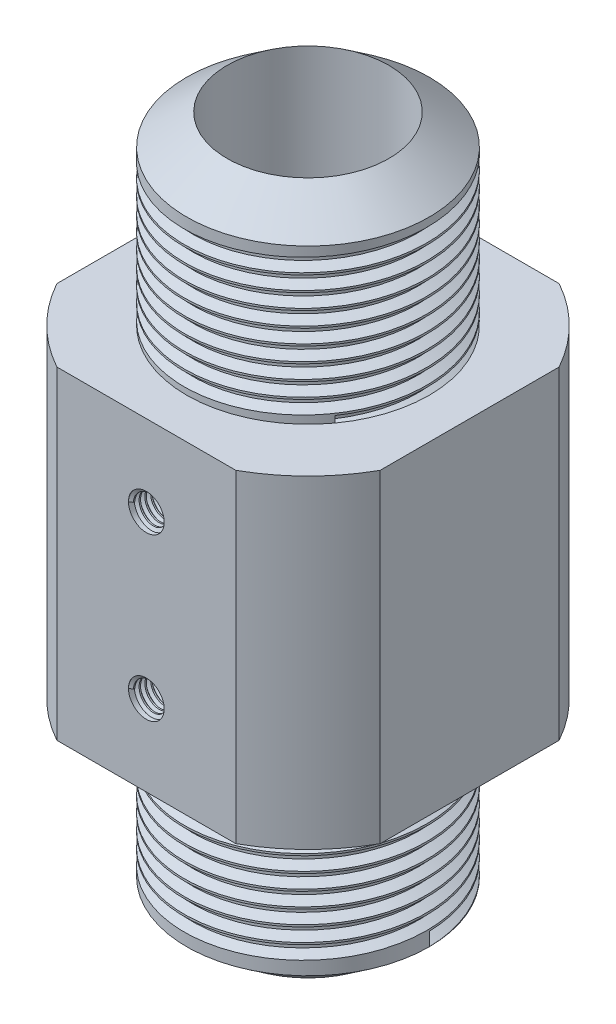
SolidWorks part; units mm, degrees
material "Plain Carbon Steel"
ref_plane "Front Plane" through (0, 0, 0) normal (0, 0, 1) x (1, 0, 0)
ref_plane "Top Plane" through (0, 0, 0) normal (0, 1, 0) x (1, 0, 0)
ref_plane "Right Plane" through (0, 0, 0) normal (1, 0, 0) x (0, 0, -1)
sketch "Sketch1" plane through (0, 0, 0) normal (0, 1, 0) x (1, 0, 0)
  circle A0 centre (0, 0) radius 25.4
  circle A1 centre (0, 0) radius 11.1125
  dimension "D1" = 50.8
  dimension "D2" = 22.225
extrude "Boss-Extrude1" add sketch "Sketch1" along normal blind 44.45
sketch "Sketch2" plane through (0, 44.45, 0) normal (0, 1, 0) x (1, 0, 0)
  circle A0 centre (0, 0) radius 11.1125
  circle A1 centre (0, 0) radius 16.6687
  dimension "D1" = 33.3375
  dimension "D2" = 22.225
extrude "Boss-Extrude2" add sketch "Sketch2" along normal blind 25.4
sketch "Sketch3" plane through (0, 0, 0) normal (1, 0, 0) x (0, 0, -1)
  line L4 (0, 69.85) -> (0, 112.4896) construction
  line L5 (16.6687, 69.85) -> (-16.6687, 69.85) construction
  line L15 (16.6687, 69.85) -> (16.6687, 65.6631)
  line L18 (11.1125, 69.85) -> (16.6687, 65.6631)
  line L19 (16.6687, 69.85) -> (11.1125, 69.85)
  dimension "D1" = 37
revolve "Cut-Revolve1" cut sketch "Sketch3" angle 360 about L4
ref_plane "Plane3" through (0, 22.225, 0) normal (0, 1, 0) x (1, 0, 0)
sketch "Sketch4" plane through (0, 44.45, 0) normal (0, 1, 0) x (1, 0, 0)
  line L0 (0, -22.225) -> (0, -25.4) construction
  line L7 (12.2967, -22.225) -> (-12.2967, -22.225)
  circle A0 centre (0, 0) radius 25.4 construction
  arc A3 (-12.2967, -22.225) -> (12.2967, -22.225) centre (0, 0) ccw
  dimension "D1" = 3.175
extrude "Cut-Extrude1" cut sketch "Sketch4" against normal blind 44.45
sketch "Sketch8" plane through (0, 0, 0) normal (0, 0, 1) x (1, 0, 0)
  line L2 (-12.6658, 0) -> (-25.4, 3.175)
  line L4 (0, 0) -> (0, 3.175) construction
  line L5 (-45.7074, 3.175) -> (45.7074, 3.175) construction
  line L8 (0, 0) -> (-12.6658, 0)
  line L9 (-25.4, 0) -> (25.4, 0) construction
  line L10 (-12.6658, 0) -> (-12.6658, 3.175) construction
  line L11 (-25.4, 3.175) -> (-25.4, -4.4695)
  line L12 (-25.4, -4.4695) -> (0, -4.4695)
  line L13 (0, -4.4695) -> (0, 0)
  line L14 (-25.4, 44.45) -> (-25.4, 0) construction
  point P5 (0, 3.175)
  dimension "D1" = 3.175
  dimension "D2" = 14
sketch "Sketch13" plane through (0, 0, 0) normal (1, 0, 0) x (0, 0, -1)
  line L0 (0, 69.85) -> (0, 124.3107)
  line L1 (11.1125, 69.85) -> (-11.1125, 69.85) construction
  line L2 (-81.28, 205.5907) -> (-649.0287, 205.5907)
  line L3 (-730.3087, 124.3107) -> (-730.3087, -599.1105)
  arc A0 (-649.0287, 205.5907) -> (-730.3087, 124.3107) centre (-649.0287, 124.3107) ccw
  arc A1 (0, 124.3107) -> (-81.28, 205.5907) centre (-81.28, 124.3107) ccw
  dimension "D1" = 81.28
sweep "Sweep1" [suppressed] add path "Sketch13" circular profile diameter 25.4 parameters "D3"=25.4
sketch "Sketch19" plane through (0, 44.45, 0) normal (0, 1, 0) x (1, 0, 0)
  line L0 (22.225, 12.2967) -> (22.225, -12.2967)
  line L1 (22.225, 0) -> (25.4, 0) construction
  arc A0 (12.2967, -22.225) -> (-12.2967, -22.225) centre (0, 0) ccw construction
  arc A1 (22.225, 12.2967) -> (22.225, -12.2967) centre (0, 0) cw
  dimension "D1" = 3.175
extrude "Cut-Extrude2" cut sketch "Sketch19" against normal up to surface (44.45 mm away) up to face at (0, 0, -1.5875)
pattern_circular "CirPattern2" count 3 every 90 about axis through (0, 44.45, 0) along (0, 1, 0) of "Cut-Extrude2"
mirror "Mirror1" about plane through (0, 22.225, 0) normal (0, 1, 0) of "Cut-Revolve1", "Boss-Extrude2"
thread "Thread2" pitch 2.1167 method cut profile "Thread Profile2" start angle 0, offset 0, length 20.32, pitch 2.1167, diameter 33.3375
ref_plane "Plane2" through (-16.6687, 65.6631, 0) normal (0, 0, 1) x (-1, 0, 0)
sketch "Thread Profile2" plane through (-16.6687, 65.6631, 0) normal (0, 0, 1) x (-1, 0, 0)
  line L0 (0, 0) -> (0, 2.1167) construction
  line L11 (0, 0) -> (0, 1.8521)
  line L12 (0, 1.8521) -> (-1.1457, 1.1906)
  line L13 (-1.1457, 1.1906) -> (-1.1457, 0.6615)
  line L15 (-1.1457, 0.6615) -> (0, 0)
  line L17 (-1.1457, 0.926) -> (0, 0.926) construction
  point P2 (0, 0)
  dimension "Pitch" = 2.1167
  dimension "Profile_Angle" = 60
  dimension "Profile_Land" = 0.5292
  dimension "Profile_Height" = 1.1457
thread "Thread3" pitch 2.1167 method cut profile "Thread Profile3" start angle 0, offset 0, length 20.32, pitch 2.1167, diameter 33.3375
ref_plane "Plane4" through (16.6687, -21.2131, 0) normal (0, 0, 1) x (1, 0, 0)
sketch "Thread Profile3" plane through (16.6687, -21.2131, 0) normal (0, 0, 1) x (1, 0, 0)
  line L0 (0, 0) -> (0, 2.1167) construction
  line L11 (0, 0) -> (0, 1.8521)
  line L12 (0, 1.8521) -> (-1.1457, 1.1906)
  line L13 (-1.1457, 1.1906) -> (-1.1457, 0.6615)
  line L15 (-1.1457, 0.6615) -> (0, 0)
  line L17 (-1.1457, 0.926) -> (0, 0.926) construction
  point P2 (0, 0)
  dimension "Pitch" = 2.1167
  dimension "Profile_Angle" = 60
  dimension "Profile_Land" = 0.5292
  dimension "Profile_Height" = 1.1457
hole_wizard "#10 (0.1935) Diameter Hole1" positions "Sketch23" profile "Sketch26" hole size "#10" standard "ANSI Inch"
sketch "Sketch23" plane through (0, 0, 22.225) normal (0, 0, 1) x (1, 0, 0)
  line L0 (0, 44.45) -> (0, 33.3375) construction
  line L1 (12.2967, 44.45) -> (-12.2967, 44.45) construction
  line L3 (0, 11.1125) -> (0, 0) construction
  line L4 (-12.2967, 22.225) -> (12.2967, 22.225) construction
  line L5 (-12.2967, 0) -> (-12.2967, 44.45) construction
  line L6 (12.2967, 0) -> (12.2967, 44.45) construction
  line L8 (0, 33.3375) -> (0, 22.225) construction
  line L9 (0, 22.225) -> (0, 11.1125) construction
  point P0 (0, 33.3375)
  point P2 (0, 11.1125)
sketch "Sketch26" plane through (0, 33.3375, 22.225) normal (1, 0, 0) x (0, -1, 0)
  line L0 (0, 0) -> (0, 8.5886)
  line L1 (0, 8.5886) -> (2.4574, 7.112)
  line L2 (2.4574, 7.112) -> (2.4574, 0)
  line L5 (2.4574, 0) -> (0, 0)
  line L10 (0, 8.5886) -> (-2.4575, 7.112) construction
  line L11 (0, -6.35) -> (0, 107.95) construction
  dimension "Hole Dia." = 4.9149
  dimension "Hole Depth" = 7.112
  dimension "Drill Angle" = 118
thread "Thread4" pitch 0.7937 method extrude profile "Thread Profile4" start angle 0, offset 0, length 6.35, pitch 0.7937, diameter 4.9149
ref_plane "Plane5" through (-2.4574, 33.3375, 22.225) normal (0, -1, 0) x (-1, 0, 0)
sketch "Thread Profile4" plane through (-2.4574, 33.3375, 22.225) normal (0, -1, 0) x (-1, 0, 0)
  line L0 (0, 0) -> (0, 0.7937) construction
  line L11 (0, 0) -> (0, 0.6945)
  line L12 (0, 0.6945) -> (-0.4296, 0.4465)
  line L13 (-0.4296, 0.4465) -> (-0.4296, 0.248)
  line L15 (-0.4296, 0.248) -> (0, 0)
  line L17 (-0.4296, 0.3473) -> (0, 0.3473) construction
  point P2 (0, 0)
  dimension "Pitch" = 0.7937
  dimension "Profile_Angle" = 60
  dimension "Profile_Land" = 0.1984
  dimension "Profile_Height" = 0.4296
thread "Thread5" pitch 0.7937 method extrude profile "Thread Profile5" start angle 0, offset 0, length 6.35, pitch 0.7937, diameter 4.9149
ref_plane "Plane6" through (-2.4574, 11.1125, 22.225) normal (0, -1, 0) x (-1, 0, 0)
sketch "Thread Profile5" plane through (-2.4574, 11.1125, 22.225) normal (0, -1, 0) x (-1, 0, 0)
  line L0 (0, 0) -> (0, 0.7937) construction
  line L11 (0, 0) -> (0, 0.6945)
  line L12 (0, 0.6945) -> (-0.4296, 0.4465)
  line L13 (-0.4296, 0.4465) -> (-0.4296, 0.248)
  line L15 (-0.4296, 0.248) -> (0, 0)
  line L17 (-0.4296, 0.3473) -> (0, 0.3473) construction
  point P2 (0, 0)
  dimension "Pitch" = 0.7937
  dimension "Profile_Angle" = 60
  dimension "Profile_Land" = 0.1984
  dimension "Profile_Height" = 0.4296
